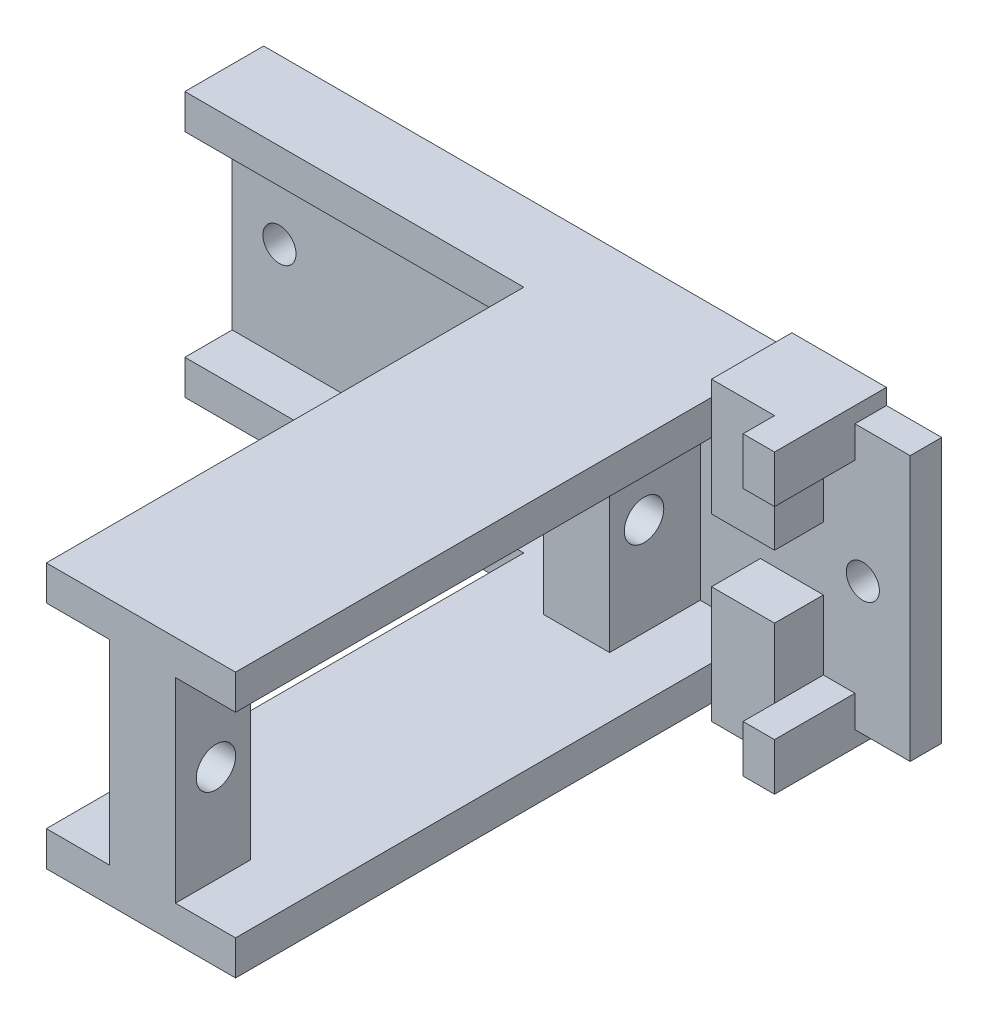
SolidWorks part; units mm, degrees
ref_plane "前视基准面" through (0, 0, 0) normal (0, 0, 1) x (1, 0, 0)
ref_plane "上视基准面" through (0, 0, 0) normal (0, 1, 0) x (1, 0, 0)
ref_plane "右视基准面" through (0, 0, 0) normal (1, 0, 0) x (0, 0, -1)
other "Configuration Table"
sketch "草图1" plane through (0, 0, 0) normal (0, 0, 1) x (1, 0, 0)
  line L1 (-23.7325, 16.5234) -> (13.7675, 16.5234)
  line L2 (-23.7325, 16.5234) -> (-23.7325, -0.2766)
  line L3 (-23.7325, -0.2766) -> (13.7675, -0.2766)
  line L4 (19.2675, 16.5234) -> (19.2675, -0.2766)
  line L9 (5.9575, 8.1234) -> (-7.3948, 8.1234) construction
  line L10 (13.7675, 5.698) -> (13.7675, 11.8935) construction
  line L22 (13.7675, 16.5234) -> (19.2675, 16.5234)
  line L23 (13.7675, -0.2766) -> (19.2675, -0.2766)
  circle A0 centre (16.2675, 8.1234) radius 1.05
  circle A1 centre (-20.7325, 8.1234) radius 1.05
  dimension "D4" = 2.1
  dimension "D5" = 2.1
  dimension "D6" = 3
  dimension "D7" = 3
  dimension "D1" = 16.8
  dimension "D2" = 43
  dimension "D3" = 5.5
extrude "凸台-拉伸1" add sketch "草图1" along normal blind 2
sketch "草图2" plane through (0, 0, 2) normal (0, 0, 1) x (1, 0, 0)
  line L0 (-23.7325, 16.5234) -> (-23.7325, -0.2766) construction
  line L1 (-23.7325, 16.5234) -> (9.7675, 16.5234)
  line L2 (-23.7325, 16.5234) -> (-23.7325, 14.3194)
  line L3 (-23.7325, 14.3194) -> (9.7675, 14.3194)
  line L4 (9.7675, 16.5234) -> (9.7675, 14.3194)
  line L5 (-23.7325, 1.9274) -> (9.7675, 1.9274)
  line L6 (-23.7325, 1.9274) -> (-23.7325, -0.2766)
  line L7 (-23.7325, -0.2766) -> (9.7675, -0.2766)
  line L8 (9.7675, 1.9274) -> (9.7675, -0.2766)
  line L9 (-23.7325, -0.2766) -> (19.2675, -0.2766) construction
  line L10 (9.7675, 3.1234) -> (9.7675, 13.1234) construction
  line L11 (-15.2515, 2.0274) -> (-0.6973, 2.0274) construction
  line L12 (-0.6973, 14.2194) -> (-15.2515, 14.2194) construction
  dimension "D1" = 0.1
  dimension "D2" = 0.1
extrude "凸台-拉伸2" add sketch "草图2" along normal up to surface (33.2834 mm away)
sketch "草图3" plane through (0, 0, 2) normal (0, 0, 1) x (1, 0, 0)
  line L0 (-23.7325, 14.3194) -> (9.7675, 14.3194) construction
  line L1 (1.7649, 14.3194) -> (5.9575, 14.3194)
  line L2 (1.7649, 14.3194) -> (1.7649, 1.9274)
  line L3 (1.7649, 1.9274) -> (5.9575, 1.9274)
  line L4 (5.9575, 14.3194) -> (5.9575, 1.9274)
  line L5 (9.7675, 1.9274) -> (-23.7325, 1.9274) construction
  line L8 (5.9575, 8.1234) -> (5.9575, 13.5844) construction
  line L9 (1.6649, 8.7584) -> (1.6649, 13.5844) construction
  dimension "D1" = 0.1
extrude "凸台-拉伸3" add sketch "草图3" along normal offset from surface (5.7514 mm away) 0.1
extrude "凸台-拉伸4" add sketch "草图3<2>" against normal offset from surface (4.7514 mm away) 0.1 from surface starting at face at (-6.9825, 15.4214, 35.2834)
sketch "草图3<2>" plane through (0, 0, 2) normal (0, 0, 1) x (1, 0, 0) same geometry as "草图3"
sketch "草图4" plane through (5.9575, 0, 0) normal (1, 0, 0) x (0, 0, -1)
  circle A0 centre (-32.718, 8.1234) radius 1.25
  circle A1 centre (-5.5654, 8.1234) radius 1.25
  dimension "D1" = 2.5
extrude "切除-拉伸1" cut sketch "草图4" against normal up to next
sketch "草图6" plane through (0, 0, 2) normal (0, 0, 1) x (1, 0, 0)
  line L0 (19.2675, 16.5234) -> (9.7675, 16.5234) construction
  line L1 (9.7675, 17.5234) -> (15.7675, 17.5234)
  line L2 (9.7675, 17.5234) -> (9.7675, 10.1234)
  line L3 (9.7675, 10.1234) -> (13.7675, 10.1234)
  line L4 (13.7675, 16.5234) -> (13.7675, 10.1234)
  line L5 (15.7675, -1.2766) -> (9.7675, -1.2766)
  line L6 (13.7675, -0.2766) -> (13.7675, 6.1234)
  line L7 (13.7675, 6.1234) -> (9.7675, 6.1234)
  line L8 (9.7675, -1.2766) -> (9.7675, 6.1234)
  line L11 (13.7675, 16.5234) -> (15.7675, 16.5234)
  line L12 (15.7675, 17.5234) -> (15.7675, 16.5234)
  line L13 (9.7675, 14.3194) -> (9.7675, 16.5234) construction
  line L14 (13.7675, -0.2766) -> (15.7675, -0.2766)
  line L17 (15.7675, -0.2766) -> (15.7675, -1.2766)
  line L18 (9.7675, 16.5234) -> (-23.7325, 16.5234) construction
  line L19 (9.7675, -0.2766) -> (19.2675, -0.2766) construction
  dimension "D1" = 4
  dimension "D2" = 2
  dimension "D3" = 1
  dimension "D4" = 4
extrude "凸台-拉伸5" add sketch "草图6" along normal blind 3.1 and the other way up to surface (2 mm away) other way up to face at (-2.2325, 8.1234, 0)
sketch "草图7" plane through (0, 0, 5.1) normal (0, 0, 1) x (1, 0, 0)
  line L0 (15.7675, 17.5234) -> (9.7675, 17.5234) construction
  line L1 (15.7675, 14.5234) -> (13.7675, 14.5234)
  line L2 (15.7675, 14.5234) -> (15.7675, 17.5234)
  line L3 (15.7675, 17.5234) -> (13.7675, 17.5234)
  line L4 (13.7675, 14.5234) -> (13.7675, 17.5234)
  line L5 (13.7675, 10.1234) -> (13.7675, 16.5234) construction
  line L6 (15.7675, -1.2766) -> (13.7675, -1.2766)
  line L7 (15.7675, -1.2766) -> (15.7675, 1.7234)
  line L8 (15.7675, 1.7234) -> (13.7675, 1.7234)
  line L9 (13.7675, -1.2766) -> (13.7675, 1.7234)
  line L10 (9.7675, -1.2766) -> (15.7675, -1.2766) construction
  dimension "D1" = 3
  dimension "D2" = 2
extrude "凸台-拉伸6" add sketch "草图7" along normal offset from surface (5.1 mm away) 2 from surface up to face at (12.2675, 1.3489, 5.1) offset beyond the face yes starting at face at (12.5803, 8.1234, 2)
sketch "草图8" plane through (0, 0, 35.2834) normal (0, 0, 1) x (1, 0, 0)
  line L0 (-23.7325, -0.2766) -> (9.7675, -0.2766) construction
  line L1 (-23.7325, 16.5234) -> (-2.2351, 16.5234)
  line L2 (-23.7325, 16.5234) -> (-23.7325, -0.2766)
  line L3 (-23.7325, -0.2766) -> (-2.2351, -0.2766)
  line L4 (-2.2351, 16.5234) -> (-2.2351, -0.2766)
  line L5 (1.7649, 1.9274) -> (1.7649, 14.3194) construction
  dimension "D1" = 4
extrude "切除-拉伸2" cut sketch "草图8" against normal offset from surface (30.2834 mm away) 5 up to face at (7.7675, 8.1234, 0)
